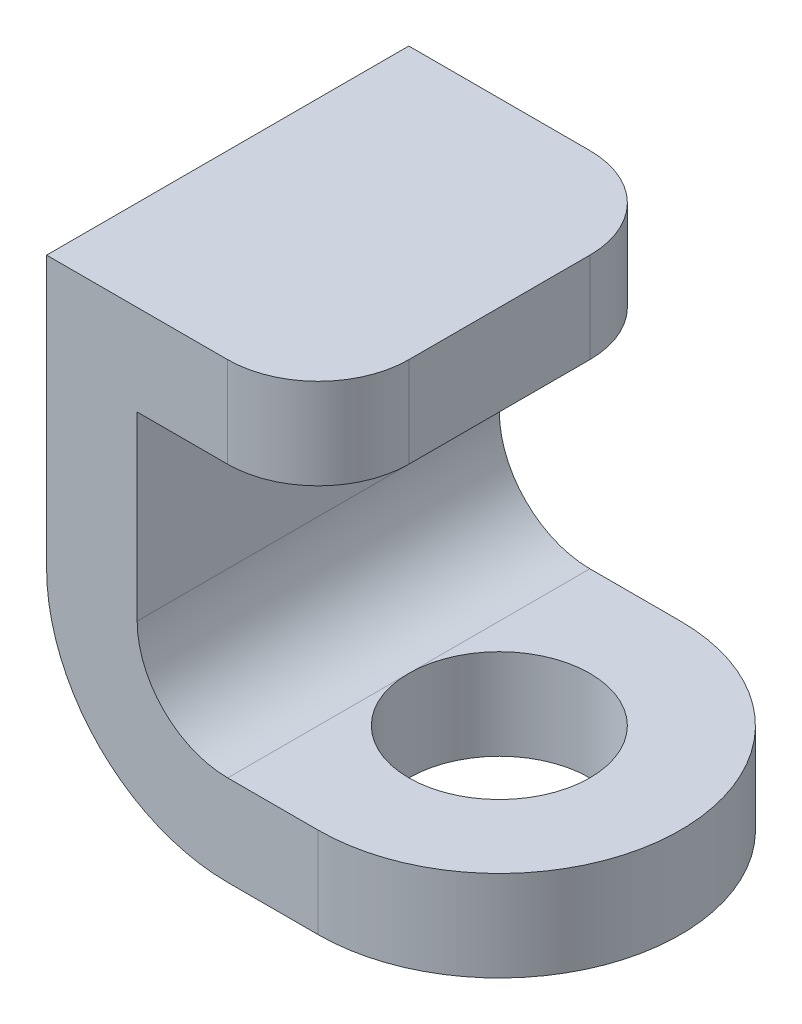
SolidWorks part; units mm, degrees
ref_plane "前基準面" through (0, 0, 0) normal (0, 0, 1) x (1, 0, 0)
ref_plane "上基準面" through (0, 0, 0) normal (0, 1, 0) x (1, 0, 0)
ref_plane "右基準面" through (0, 0, 0) normal (1, 0, 0) x (0, 0, -1)
sketch "草圖1" plane through (0, 0, 0) normal (0, 1, 0) x (1, 0, 0)
  line L0 (0, 10) -> (-15, 10)
  line L1 (-15, 10) -> (-15, -10)
  line L2 (-15, -10) -> (0, -10)
  line L3 (0, -10) -> (-10, -10)
  line L4 (-10, -10) -> (-10, 10)
  circle A0 centre (0, 0) radius 5
  arc A1 (0, -10) -> (0, 10) centre (0, 0) ccw
  dimension "D1" = 20
  dimension "D2" = 10
  dimension "D3" = 15
  dimension "D4" = 5
extrude "填料-伸長1" add sketch "草圖1" along normal blind 5 contours L2 A1 L0 L4 A0 region at (9.7172, 0, 0)
extrude "填料-伸長2" add sketch "草圖1<3>" along normal blind 25 contours L2 L4 L0 L1 region at (-12.5, 0, 0)
sketch "草圖1<3>" plane through (0, 0, 0) normal (0, 1, 0) x (1, 0, 0) same geometry as "草圖1"
sketch "草圖2" plane through (-10, 0, 0) normal (1, 0, 0) x (0, 0, -1)
  line L0 (10, 25) -> (10, 5) construction
  line L1 (-10, 25) -> (10, 25)
  line L2 (-10, 25) -> (-10, 20)
  line L3 (-10, 20) -> (10, 20)
  line L4 (10, 25) -> (10, 20)
  dimension "D1" = 5
extrude "填料-伸長3" add sketch "草圖2" along normal blind 10
fillet "圓角1" radius 5 2 edges at (0, 22.5, -10) (0, 22.5, 10)
fillet "圓角2" radius 10 1 edges at (-15, 0, 0)
fillet "圓角3" radius 5 1 edges at (-10, 5, 0)
